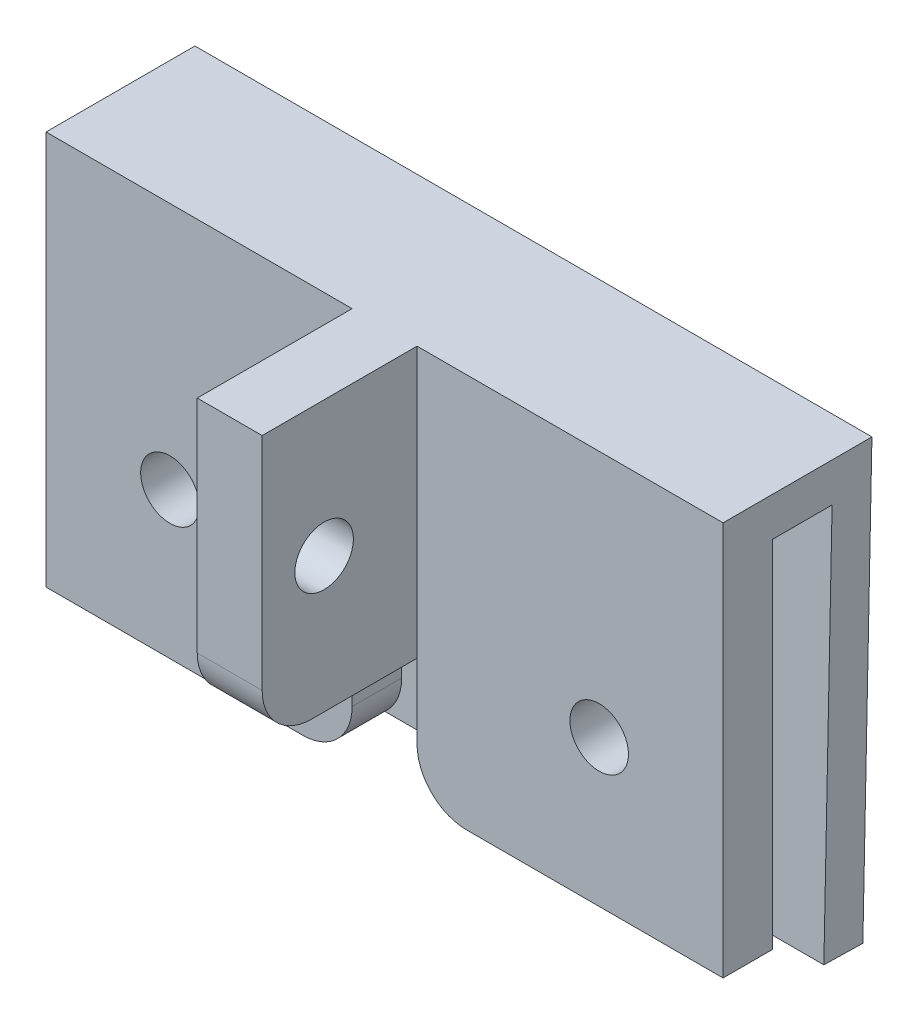
SolidWorks part; units mm, degrees
ref_plane "Front Plane" through (0, 0, 0) normal (0, 0, 1) x (1, 0, 0)
ref_plane "Top Plane" through (0, 0, 0) normal (0, 1, 0) x (1, 0, 0)
ref_plane "Right Plane" through (0, 0, 0) normal (1, 0, 0) x (0, 0, -1)
sketch "Sketch1" plane through (0, 0, 0) normal (0, 0, 1) x (1, 0, 0)
  line L0 (0, 10.102) -> (0, -10.102) construction
  line L1 (-17.35, 10.102) -> (17.35, 10.102)
  line L2 (-17.35, 10.102) -> (-17.35, -10.102)
  line L3 (-17.35, -10.102) -> (17.35, -10.102)
  line L4 (17.35, 10.102) -> (17.35, -10.102)
  line L5 (-17.35, -3.752) -> (17.35, -3.752) construction
  line L6 (-1.6637, -10.102) -> (-1.6637, -3.752)
  line L7 (-1.6637, -3.752) -> (1.6637, -3.752)
  line L8 (1.6637, -3.752) -> (1.6637, -10.102)
  line L9 (-11, -2.598) -> (11, -2.598) construction
  circle A0 centre (-11, -2.598) radius 1.5
  circle A1 centre (11, -2.598) radius 1.5
  point P6 (1.9004, -0.577)
  point P14 (0, -3.752)
  point P19 (0, -2.598)
  point P23 (0, 0)
  dimension "D3" = 3
  dimension "D1" = 22
  dimension "D2" = 1.154
  dimension "D4" = 12.7
  dimension "D5" = 6.35
  dimension "D6" = 3.3274
  dimension "D7" = 6.35
extrude "Boss-Extrude1" add sketch "Sketch1" along normal blind 2.54 contours L7 L8 L3 L4 L1 L2 L6 A1 A0 region at (0, 0.275, 0)
sketch "Sketch2" plane through (0, 0, 2.54) normal (0, 0, 1) x (1, 0, 0)
  line L0 (-17.35, 10.102) -> (17.35, 10.102) construction
  line L1 (-1.6637, -3.752) -> (1.6637, -3.752)
  line L2 (-1.6637, -3.752) -> (-1.6637, 10.102)
  line L3 (-1.6637, 10.102) -> (1.6637, 10.102)
  line L4 (1.6637, -3.752) -> (1.6637, 10.102)
  point P7 (1.6637, -0.577)
extrude "Boss-Extrude2" add sketch "Sketch2" along normal blind 7.9375
sketch "Sketch3" plane through (-1.6637, 0, 0) normal (-1, 0, 0) x (0, 0, 1)
  line L0 (10.4775, 10.102) -> (10.4775, -3.752) construction
  line L2 (2.54, 10.102) -> (2.54, -10.102) construction
  circle A1 centre (7.3025, 3.175) radius 1.5
  point P0 (5.5663, 2.9611)
  point P5 (10.4775, 3.175)
  dimension "D1" = 3
  dimension "D2" = 4.7625
extrude "Cut-Extrude1" cut sketch "Sketch3" against normal through all
fillet "Fillet1" radius 2.54 1 edges at (0, -3.752, 10.4775)
fillet "Fillet3" radius 2.54 2 edges at (1.6637, -10.102, 1.27) (-1.6637, -10.102, 1.27)
sketch "Sketch4" plane through (17.35, 0, 0) normal (1, 0, 0) x (0, 0, -1)
  line L0 (0, 10.102) -> (5.0903, 10.102)
  line L1 (5.0903, 10.102) -> (4.6666, -10.1438)
  line L2 (4.6666, -10.1438) -> (2.667, -10.102)
  line L3 (2.667, -10.102) -> (3.048, 8.102)
  line L4 (3.048, 8.102) -> (0, 8.102)
  line L5 (0, 10.102) -> (0, -10.102) construction
  line L6 (4.6666, -10.1438) -> (4.6247, -12.1434)
  line L7 (4.6247, -12.1434) -> (2.6252, -12.1016)
  line L8 (2.6252, -12.1016) -> (2.667, -10.102)
  point P7 (2.667, -12.3416)
  point P8 (1.07, -12.1806)
  line M9 (0, -10.102) -> (0, 10.102)
  dimension "D1" = 2
  dimension "D2" = 2
  dimension "D3" = 3.048
  dimension "D4" = 2.667
  dimension "D5" = 2
extrude "Boss-Extrude3" add sketch "Sketch4" against normal up to surface (34.7 mm away) contours L8 L7 L6 L2 | L4 L3 L2 L1 L0 M9 region at (17.35, 1.1902, -3.57) region at (17.35, -11.1227, -3.6459) up to face at (-17.35, 0, 1.27)
equation "\"bottomThickness\"= .220in"
equation "\"wallThickness\"= .125in"
equation "\"D6@Sketch1\"=\"wallThickness\"+.006in"
equation "\"D3@Sketch4\"=\"wallThickness\"-.005in"
equation "\"D4@Sketch4\"=\"wallThickness\"-.02in"
